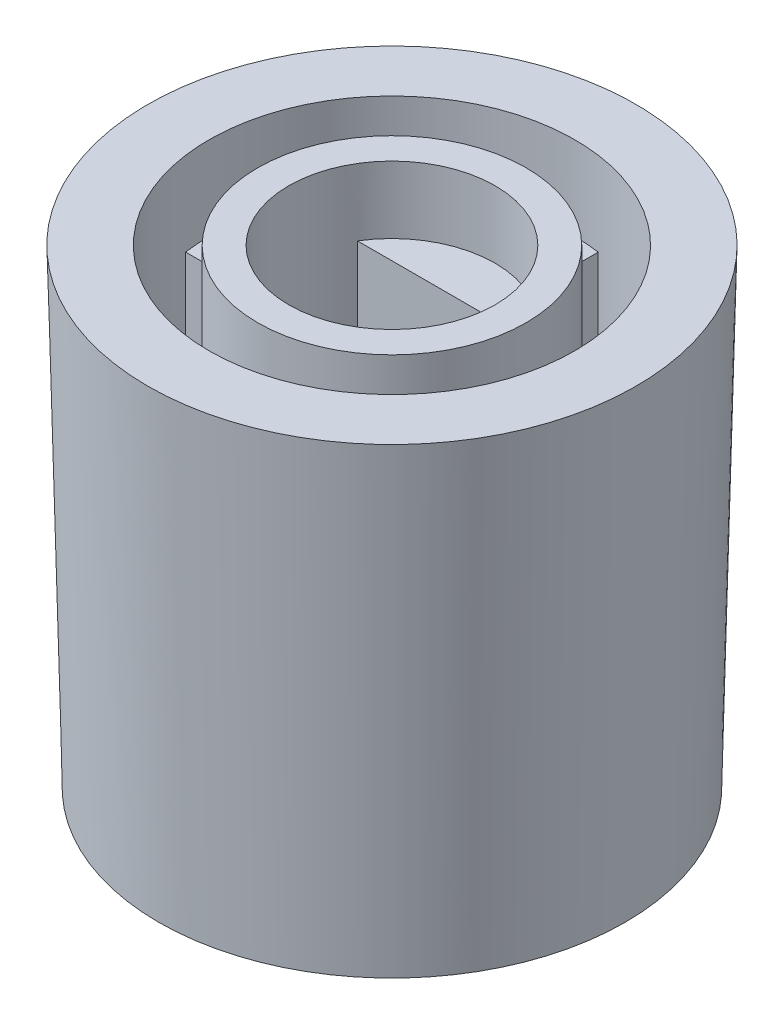
SolidWorks part; units mm, degrees
ref_plane "Front Plane" through (0, 0, 0) normal (0, 0, 1) x (1, 0, 0)
ref_plane "Top Plane" through (0, 0, 0) normal (0, 1, 0) x (1, 0, 0)
ref_plane "Right Plane" through (0, 0, 0) normal (1, 0, 0) x (0, 0, -1)
sketch "Sketch1" plane through (0, 0, 0) normal (0, 1, 0) x (1, 0, 0)
  circle A0 centre (0, 0) radius 6.95
  dimension "D1" = 13.9
extrude "Boss-Extrude1" add sketch "Sketch1" along normal blind 3.5
sketch "Sketch2" plane through (0, 3.5, 0) normal (0, 1, 0) x (1, 0, 0)
  circle A0 centre (0, 0) radius 6.95
  circle A1 centre (0, 0) radius 5.45
  dimension "D1" = 13.9
  dimension "D2" = 10.9
extrude "Boss-Extrude2" add sketch "Sketch2" along normal blind 10.5
draft "Draft1" type of draft neutral plane draft angle 1.325 faces to draft 1 face at (0, 0, 6.95) neutral plane through (0, 0, 0) neutral plane normal (0, -1, 0) parameters "D1"=1.325
sketch "Sketch6" plane through (0, 3.5, 0) normal (0, 1, 0) x (1, 0, 0)
  circle A0 centre (0, 0) radius 4
  dimension "D1" = 8
extrude "Boss-Extrude3" add sketch "Sketch6" along normal blind 10.5
sketch "Sketch5" plane through (0, 14, 0) normal (0, 1, 0) x (1, 0, 0)
  line L0 (-2.626, 1.6) -> (2.626, 1.6)
  circle A0 centre (0, 0) radius 3.075
  dimension "D1" = 6.15
  dimension "D2" = 1.6
extrude "Cut-Extrude1" cut sketch "Sketch5" against normal blind 9 contours L0 A0 region at (0, 14, 0.4982)
sketch "Sketch7" plane through (0, 14, 0) normal (0, 1, 0) x (1, 0, 0)
  circle A0 centre (0, 0) radius 3.075
  dimension "D1" = 6.15
extrude "Cut-Extrude2" cut sketch "Sketch7" against normal blind 2
sketch "Sketch8" plane through (0, 3.5, 0) normal (0, 1, 0) x (1, 0, 0)
  line L1 (-6.116, 0.75) -> (-3.5908, 0.75)
  line L2 (-6.116, 0.75) -> (-6.116, -0.75)
  line L3 (-6.116, -0.75) -> (-3.5908, -0.75)
  line L4 (-3.5908, 0.75) -> (-3.5908, -0.75)
  line L5 (3.6356, 0.75) -> (5.7578, 0.75)
  line L6 (3.6356, 0.75) -> (3.6356, -0.75)
  line L7 (3.6356, -0.75) -> (5.7578, -0.75)
  line L8 (5.7578, 0.75) -> (5.7578, -0.75)
  line L9 (-0.75, 3.5774) -> (0.75, 3.5774)
  line L10 (-0.75, 3.5774) -> (-0.75, 5.9145)
  line L11 (-0.75, 5.9145) -> (0.75, 5.9145)
  line L12 (0.75, 3.5774) -> (0.75, 5.9145)
  line L13 (0.75, -3.4431) -> (-0.75, -3.4431)
  line L14 (0.75, -3.4431) -> (0.75, -6.2011)
  line L15 (0.75, -6.2011) -> (-0.75, -6.2011)
  line L16 (-0.75, -3.4431) -> (-0.75, -6.2011)
  point P16 (-3.5908, 0)
  point P18 (0, 3.5774)
  dimension "D1" = 1.5
extrude "Boss-Extrude4" add sketch "Sketch8" along normal blind 8
